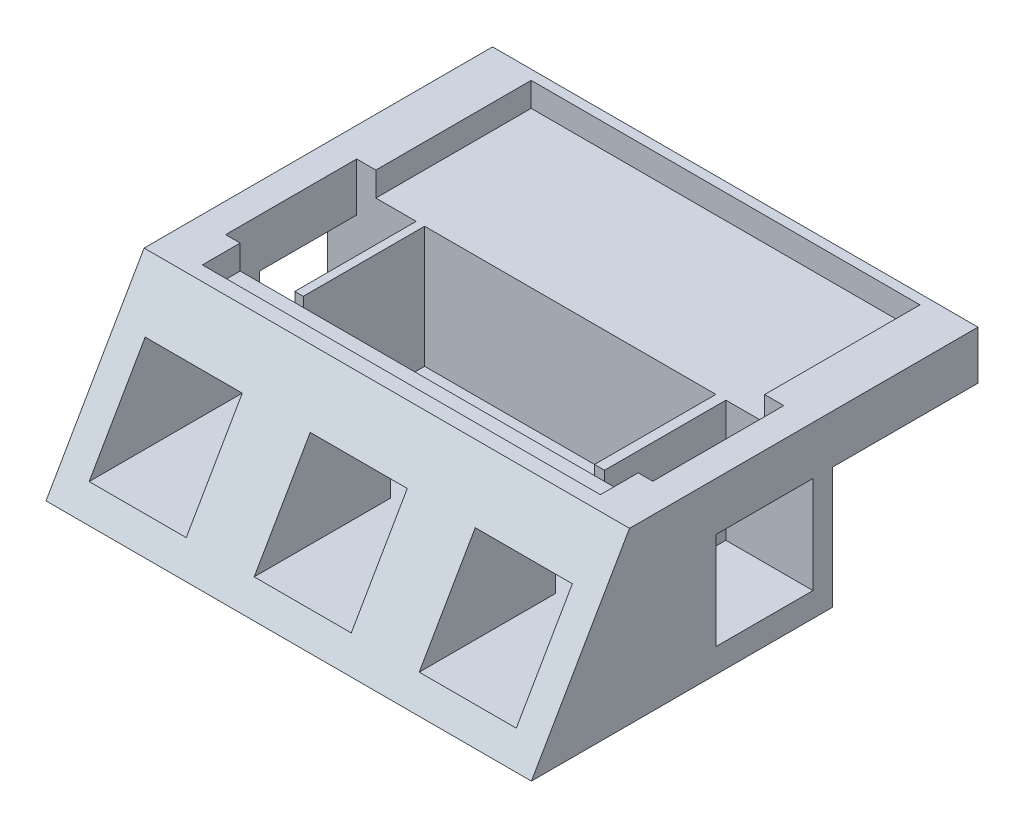
SolidWorks part; units mm, degrees
ref_plane "Alzado" through (0, 0, 0) normal (0, 0, 1) x (1, 0, 0)
ref_plane "Planta" through (0, 0, 0) normal (0, 1, 0) x (1, 0, 0)
ref_plane "Vista lateral" through (0, 0, 0) normal (1, 0, 0) x (0, 0, -1)
sketch "Croquis1" plane through (0, 0, 0) normal (0, 1, 0) x (1, 0, 0)
  line L1 (0, 0) -> (100, 0)
  line L2 (0, 0) -> (0, 62)
  line L3 (0, 62) -> (100, 62)
  line L4 (100, 0) -> (100, 62)
  dimension "D1" = 62
  dimension "D2" = 100
extrude "Saliente-Extruir1" add sketch "Croquis1" along normal blind 35
chamfer "Chaflán1" distance 35 angle 30 1 edges at (50, 35, 0) first distance on face at (50, 17.5, 0)
sketch "Croquis3" plane through (0, 0, 0) normal (0, 0, 1) x (1, 0, 0)
  line L0 (0, 0) -> (100, 0) construction
  line L1 (40, 25) -> (60, 25)
  line L2 (40, 25) -> (40, 5)
  line L3 (40, 5) -> (60, 5)
  line L4 (60, 25) -> (60, 5)
  line L5 (6, 25) -> (26, 25)
  line L6 (6, 25) -> (6, 5)
  line L7 (6, 5) -> (26, 5)
  line L8 (26, 25) -> (26, 5)
  line L9 (74, 25) -> (94, 25)
  line L10 (74, 25) -> (74, 5)
  line L11 (74, 5) -> (94, 5)
  line L12 (94, 25) -> (94, 5)
  line L13 (0, 0) -> (0, 35) construction
  line L14 (100, 35) -> (100, 0) construction
  point P14 (50, 0)
  point P15 (50, 5)
  dimension "D1" = 5
  dimension "D2" = 20
  dimension "D3" = 20
  dimension "D4" = 5
  dimension "D5" = 20
  dimension "D6" = 20
  dimension "D7" = 5
  dimension "D8" = 20
  dimension "D9" = 20
  dimension "D10" = 6
  dimension "D11" = 6
extrude "Cortar-Extruir1" cut sketch "Croquis3" against normal blind 38
sketch "Croquis4" plane through (0, 0, 0) normal (-1, 0, 0) x (0, 0, 1)
  line L0 (-35.2073, 35) -> (-35.2073, 0) construction
  line L1 (-62, 35) -> (-20.2073, 35) construction
  line L2 (-62, 0) -> (0, 0) construction
  line L3 (-62, 35) -> (-62, 0) construction
  line L4 (-58, 5) -> (-38, 5)
  line L5 (-58, 5) -> (-58, 25)
  line L6 (-58, 25) -> (-38, 25)
  line L7 (-38, 5) -> (-38, 25)
  dimension "D1" = 15
  dimension "D2" = 5
  dimension "D3" = 4
  dimension "D4" = 20
  dimension "D5" = 20
extrude "Cortar-Extruir2" cut sketch "Croquis4" against normal blind 100
sketch "Croquis7" plane through (0, 35, 0) normal (0, 1, 0) x (1, 0, 0)
  line L0 (6, 14.4338) -> (6, 2.8868) construction
  line L1 (6, 58) -> (94, 58)
  line L2 (6, 58) -> (6, 31)
  line L3 (6, 31) -> (94, 31)
  line L4 (94, 58) -> (94, 31)
  line L5 (94, 2.8868) -> (94, 14.4338) construction
  line L6 (100, 58) -> (0, 58) construction
  dimension "D1" = 27
extrude "Cortar-Extruir5" cut sketch "Croquis7" against normal blind 30
sketch "Croquis8" plane through (0, 35, 0) normal (0, 1, 0) x (1, 0, 0)
  line L0 (6, 31) -> (94, 31) construction
  line L1 (9, 31) -> (23, 31)
  line L2 (9, 31) -> (9, 23.2073)
  line L3 (9, 23.2073) -> (23, 23.2073)
  line L5 (0, 20.2073) -> (100, 20.2073) construction
  line L6 (43, 31) -> (57, 31)
  line L8 (43, 23.2073) -> (57, 23.2073)
  line L10 (77, 31) -> (91, 31)
  line L12 (77, 23.2073) -> (91, 23.2073)
  line L13 (91, 31) -> (91, 23.2073)
  line L14 (6, 38) -> (6, 2.8868) construction
  line L20 (94, 2.8868) -> (94, 14.4338) construction
  line L21 (23, 23.2073) -> (43, 23.2073)
  line L22 (57, 23.2073) -> (77, 23.2073)
  line L23 (77, 31) -> (57, 31)
  line L24 (43, 31) -> (23, 31)
  dimension "D1" = 3
  dimension "D2" = 3
  dimension "D4" = 3
  dimension "D7" = 3
  dimension "D9" = 3
extrude "Cortar-Extruir6" cut sketch "Croquis8" against normal blind 5
sketch "Croquis9" plane through (0, 5, 0) normal (0, 1, 0) x (1, 0, 0)
  line L0 (100, 58) -> (0, 58) construction
  line L2 (20, 58) -> (20, 33)
  line L4 (80, 58) -> (80, 33)
  line L9 (18.2597, 33) -> (20, 33)
  line L10 (80, 33) -> (82.0642, 33)
  line L12 (18.2597, 33) -> (18.2597, 58)
  line L13 (94, 58) -> (6, 58) construction
  line L14 (18.2597, 58) -> (20, 58)
  line L15 (82.0642, 33) -> (82.0642, 58)
  line L16 (82.0642, 58) -> (80, 58)
  dimension "D1" = 25
  dimension "D2" = 60
extrude "Saliente-Extruir2" add sketch "Croquis9" along normal blind 25
sketch "Croquis10" plane through (0, 0, -62) normal (0, 0, -1) x (-1, 0, 0)
  line L1 (-100, 35) -> (0, 35)
  line L2 (-100, 35) -> (-100, 25)
  line L3 (-100, 25) -> (0, 25)
  line L4 (0, 35) -> (0, 25)
extrude "Saliente-Extruir3" add sketch "Croquis10" along normal blind 30
sketch "Croquis11" plane through (0, 35, 0) normal (0, 1, 0) x (1, 0, 0)
  line L0 (0, 92) -> (100, 92) construction
  line L1 (9.95, 90) -> (90.05, 90)
  line L2 (9.95, 90) -> (9.95, 58)
  line L3 (9.95, 58) -> (90.05, 58)
  line L4 (90.05, 90) -> (90.05, 58)
  line L5 (94, 58) -> (6, 58) construction
  point P6 (50, 92)
  point P7 (50, 58)
  dimension "D1" = 80.1
  dimension "D2" = 2
extrude "Cortar-Extruir7" cut sketch "Croquis11" against normal blind 5
